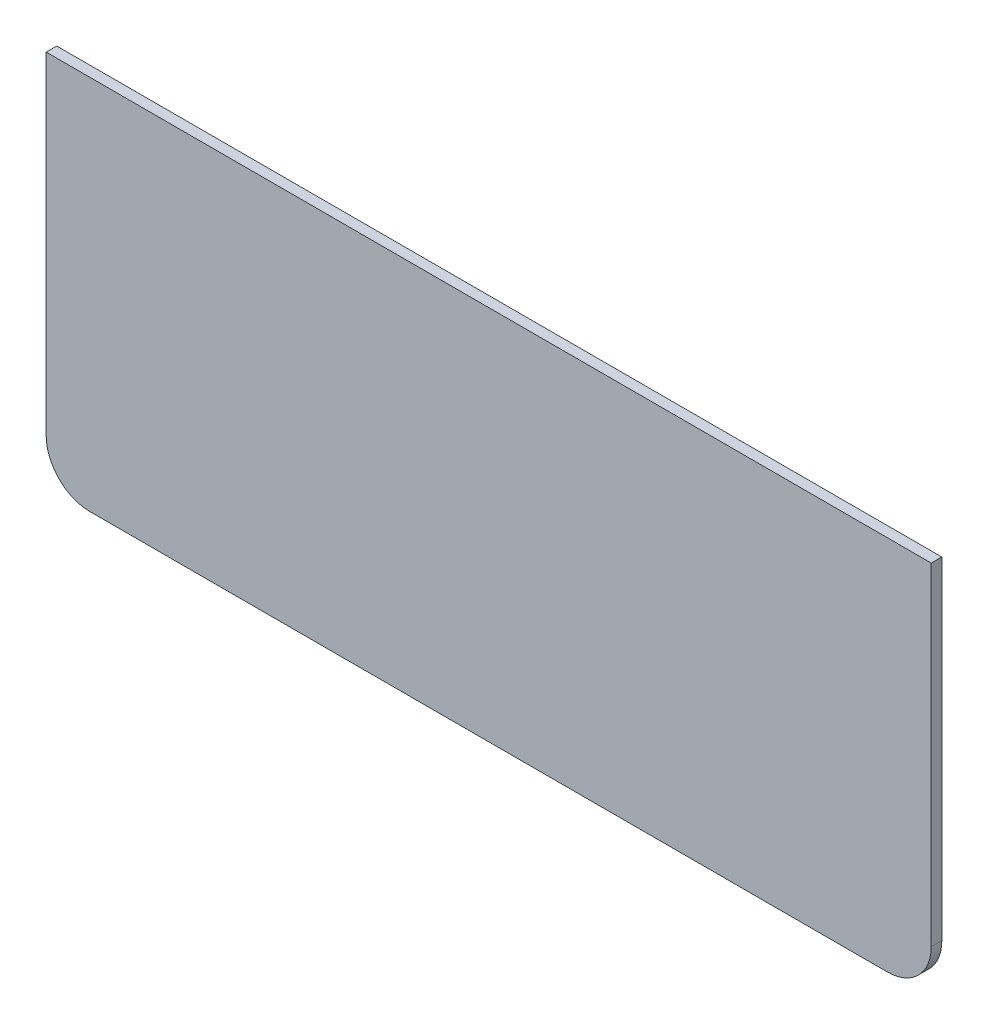
SolidWorks part; units mm, degrees
ref_plane "Front Plane" through (0, 0, 0) normal (0, 0, 1) x (1, 0, 0)
ref_plane "Top Plane" through (0, 0, 0) normal (0, 1, 0) x (1, 0, 0)
ref_plane "Right Plane" through (0, 0, 0) normal (1, 0, 0) x (0, 0, -1)
sketch "Sketch2" plane through (0, 0, 0) normal (0, 0, 1) x (1, 0, 0)
  line L0 (-53.5866, 40.5355) -> (212.7634, 40.5355)
  line L1 (212.7634, 40.5355) -> (212.7634, -72.6395)
  line L2 (212.7634, -72.6395) -> (-53.5866, -72.6395)
  line L3 (-53.5866, -72.6395) -> (-53.5866, 40.5355)
  dimension "D1" = 113.175
  dimension "D2" = 266.35
extrude "Boss-Extrude1" add sketch "Sketch2" along normal blind 3.175
fillet "Fillet1" radius 13.175 2 edges at (-53.5866, -72.6395, 1.5875) (212.7634, -72.6395, 1.5875)
equation "\"L\"= 500"
equation "\"W\"= 260"
equation "\"H\"= 110"
equation "\"Compartment Width\"= 100"
equation "\"T\"= 4.7625 * 2 / 3"
equation "\"Inside Fillet Radius\"= 10"
equation "\"D1@Fillet1\"=\"Inside Fillet Radius\"+\"T\""
equation "\"D1@Sketch2\"=\"T\"+\"H\""
equation "\"D2@Sketch2\"=2*\"T\"+\"W\""
equation "\"D1@Boss-Extrude1\"=\"T\""
